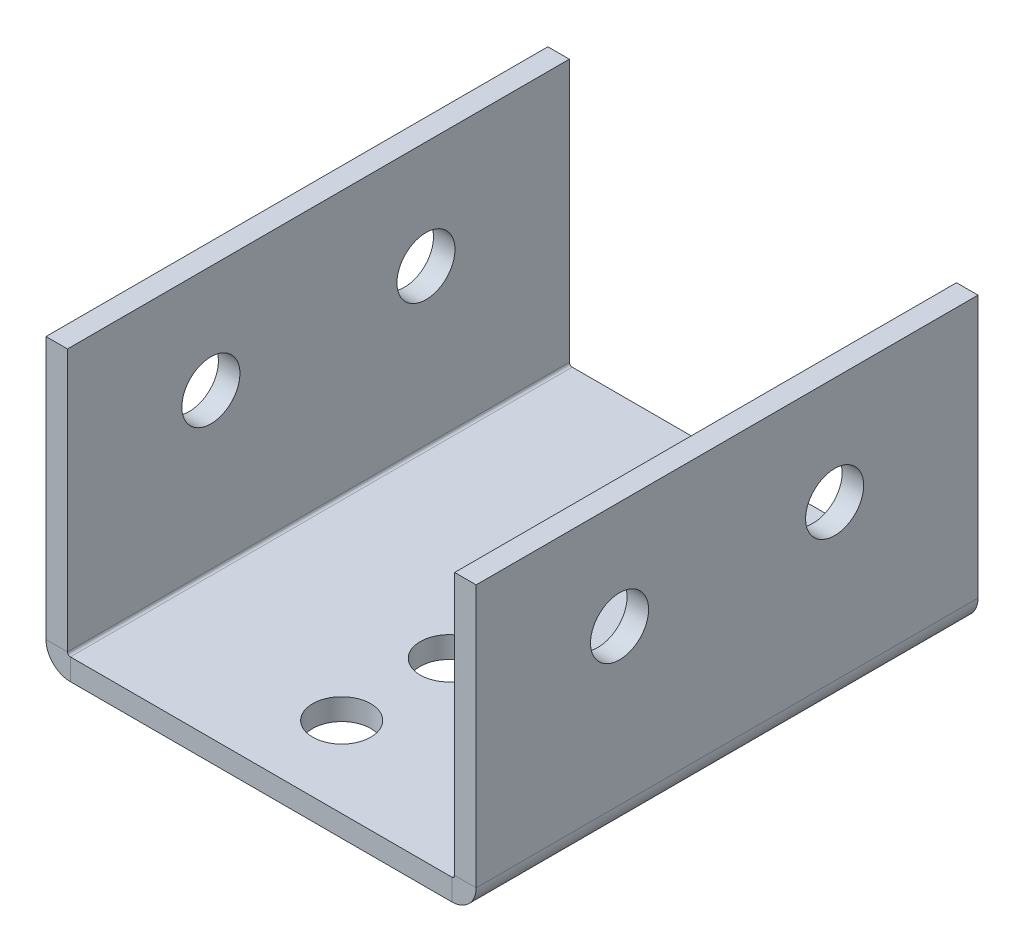
SolidWorks part; units mm, degrees
note: The reader was unsure of these and kept them because the rebuilt part matched: thickness of "Base-Flange1", "Edge-Flange1", "Sheet-Metal10", "Sheet-Metal11", "Sheet-Metal12", "Sheet-Metal13"; flange length of "Edge-Flange1".
material "6063-T6"
ref_plane "Front Plane" through (0, 0, 0) normal (0, 0, 1) x (1, 0, 0)
ref_plane "Top Plane" through (0, 0, 0) normal (0, 1, 0) x (1, 0, 0)
ref_plane "Right Plane" through (0, 0, 0) normal (1, 0, 0) x (0, 0, -1)
sketch "Sketch1" plane through (0, 0, 0) normal (0, 1, 0) x (1, 0, 0)
  line L1 (-30, 35) -> (30, 35)
  line L2 (-30, 35) -> (-30, -35)
  line L3 (-30, -35) -> (30, -35)
  line L4 (30, 35) -> (30, -35)
  line L5 (-44.2539, 0) -> (44.2539, 0) construction
  dimension "D2" = 60
  dimension "D3" = 30
  dimension "D1" = 70
  dimension "D4" = 35
base flange "Base-Flange1" sketch "Sketch1" thickness 3 reverse thickness direction no parameters "D1"=0.4
edge flange "Edge-Flange1" sketch "Sketch12" flange profiles "Sketch12", "Sketch13" flange angle 90 flange length 40 flange position material inside bend radius 0.4 thickness 3 relief rectangular parameters "D6"=10, "D8"=1
sketch "Sketch12" plane through (30, 0, 0) normal (1, 0, 0) x (0, 0, -1)
  line L2 (-35, 0) -> (-35, 37)
  line L3 (-35, 37) -> (35, 37)
  line L4 (35, 37) -> (35, 0)
  line L11 (-35, 0) -> (35, 0) construction
  line L12 (-35, 0) -> (35, 0)
sketch "Sketch13" plane through (-30, 0, 0) normal (-1, 0, 0) x (0, 0, 1)
  line L0 (-35, 0) -> (35, 0) construction
  line L1 (-35, 0) -> (35, 0)
  line L2 (-35, 0) -> (-35, 37)
  line L3 (-35, 37) -> (35, 37)
  line L4 (35, 37) -> (35, 0)
bend "EdgeBend1" bend radius 0.4 bend angle 90 parameters "D5"=1
bend "EdgeBend2" bend radius 0.4 bend angle 90 parameters "D5"=2
sketch "Sketch14" plane through (30, 0, 0) normal (1, 0, 0) x (0, 0, -1)
  line L1 (35, 37) -> (-35, 37) construction
  line L2 (-35, 37) -> (-35, 0.4) construction
  circle A0 centre (-15, 22) radius 4.05
  circle A1 centre (15, 22) radius 4.05
  dimension "D2" = 8.1
  dimension "D3" = 8.1
  dimension "D1" = 30
  dimension "D5" = 15
  dimension "D4" = 20
extrude "Cut-Extrude1" cut sketch "Sketch14" against normal up to surface (60 mm away) normal cut yes up to face at (-30, 18.7, 0)
sketch "Sketch15" plane through (0, -3, 0) normal (0, -1, 0) x (1, 0, 0)
  line L0 (0, -44.7868) -> (0, 44.7868) construction
  line L3 (26.6, -35) -> (-26.6, -35) construction
  circle A0 centre (0, 8.75) radius 4.05
  circle A1 centre (0, 23.75) radius 4.05
  dimension "D2" = 8.1
  dimension "D3" = 8.1
  dimension "D1" = 43.75
  dimension "D4" = 15
extrude "Cut-Extrude2" cut sketch "Sketch15" against normal up to surface (3 mm away) normal cut yes up to face at (0, 0, 0)
sketch "Bend-Lines1" [suppressed] plane through (0, 0, 0) normal (0, 1, 0) x (1, 0, 0)
sketch "Bounding-Box1" [suppressed] plane through (0, 0, 0) normal (0, 1, 0) x (1, 0, 0)
sheet metal parameters "Sheet-Metal10" thickness 3 parameters "D1"=1.6, "D7"=3.18
flat pattern "Flat-Pattern10" [suppressed]
sketch "Bend-Lines2" plane through (0, 0, 0) normal (0, 1, 0) x (1, 0, 0)
sketch3d "Bounding-Box2" [suppressed]
  line L0 (25.4, 30, 0) -> (25.4, -30, 0) construction
  line L1 (-25.4, 30, 0) -> (-25.4, -30, 0) construction
  line L2 (25.4, 30, 0) -> (-25.4, 30, 0) construction
  line L3 (25.4, -30, 0) -> (-25.4, -30, 0) construction
sheet metal parameters "Sheet-Metal11" thickness 3 parameters "D1"=1.6, "D7"=3.18
flat pattern "Flat-Pattern10"
sketch "Bend-Lines2" plane through (0, 0, 0) normal (0, 1, 0) x (1, 0, 0)
  line L0 (-28.0923, 35) -> (-28.0923, -35) construction
  line L1 (28.0923, -35) -> (28.0923, 35) construction
  line L2 (-28.0923, 35) -> (-28.0923, -35) construction
  line L3 (28.0923, -35) -> (28.0923, 35) construction
sketch3d "Bounding-Box2" [suppressed]
  line L0 (66.1845, -35, 0) -> (-66.1845, -35, 0) construction
  line L1 (66.1845, 35, 0) -> (-66.1845, 35, 0) construction
  line L2 (66.1845, -35, 0) -> (66.1845, 35, 0) construction
  line L3 (-66.1845, -35, 0) -> (-66.1845, 35, 0) construction
bend of the flat pattern "Flatten-<EdgeBend1>1"
bend of the flat pattern "Flatten-<EdgeBend2>1"
sheet metal parameters "Sheet-Metal12" thickness 3 parameters "D1"=1.6, "D7"=3.18
flat pattern "Flat-Pattern10"
sketch "Bend-Lines2" plane through (0, 0, 0) normal (0, 1, 0) x (1, 0, 0)
  line L0 (-28.0923, 35) -> (-28.0923, -35) construction
  line L1 (28.0923, -35) -> (28.0923, 35) construction
  line L2 (-28.0923, 35) -> (-28.0923, -35) construction
  line L3 (28.0923, -35) -> (28.0923, 35) construction
sketch3d "Bounding-Box2" [suppressed]
  line L0 (66.1845, -35, 0) -> (-66.1845, -35, 0) construction
  line L1 (66.1845, 35, 0) -> (-66.1845, 35, 0) construction
  line L2 (66.1845, -35, 0) -> (66.1845, 35, 0) construction
  line L3 (-66.1845, -35, 0) -> (-66.1845, 35, 0) construction
bend of the flat pattern "Flatten-<EdgeBend1>1"
bend of the flat pattern "Flatten-<EdgeBend2>1"
sheet metal parameters "Sheet-Metal13" thickness 3 parameters "D1"=1.6, "D7"=3.18
flat pattern "Flat-Pattern10"
sketch "Bend-Lines2" plane through (0, 0, 0) normal (0, 1, 0) x (1, 0, 0)
  line L0 (-28.0923, 35) -> (-28.0923, -35) construction
  line L1 (28.0923, -35) -> (28.0923, 35) construction
  line L2 (-28.0923, 35) -> (-28.0923, -35) construction
  line L3 (28.0923, -35) -> (28.0923, 35) construction
sketch3d "Bounding-Box2" [suppressed]
  line L0 (66.1845, -35, 0) -> (-66.1845, -35, 0) construction
  line L1 (66.1845, 35, 0) -> (-66.1845, 35, 0) construction
  line L2 (66.1845, -35, 0) -> (66.1845, 35, 0) construction
  line L3 (-66.1845, -35, 0) -> (-66.1845, 35, 0) construction
bend of the flat pattern "Flatten-<EdgeBend1>1"
bend of the flat pattern "Flatten-<EdgeBend2>1"
equation "\"width\"=60"
equation "\"D2@Sketch1\"=\"width\""
equation "\"D3@Sketch1\"=\"width\"/2"
equation "\"length\"=70"
equation "\"D1@Sketch1\"=\"length\""
equation "\"D4@Sketch1\"=\"length\"/2"
equation "\"height\"=40"
equation "\"D7@Edge-Flange1\"=\"height\""
equation "\"D4@Sketch14\"=(\"length\"-30)/2"
equation "\"D1@Sketch15\"=\"length\"/1.6"
